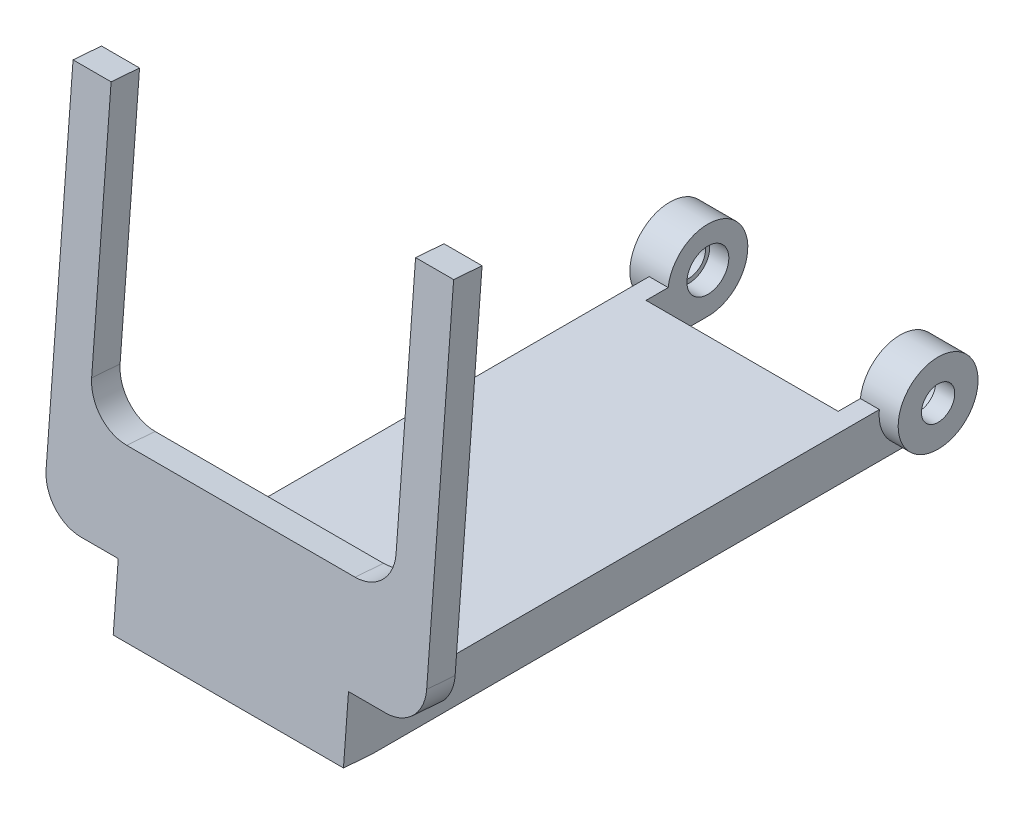
SolidWorks part; units mm, degrees
ref_plane "前视基准面" through (0, 0, 0) normal (0, 0, 1) x (1, 0, 0)
ref_plane "上视基准面" through (0, 0, 0) normal (0, 1, 0) x (1, 0, 0)
ref_plane "右视基准面" through (0, 0, 0) normal (1, 0, 0) x (0, 0, -1)
other "Configuration Table"
sketch "草图1" plane through (0, 0, 0) normal (0, 1, 0) x (1, 0, 0)
  line L1 (0, 0) -> (20.2, 0)
  line L2 (0, 0) -> (0, -30)
  line L3 (0, -30) -> (20.2, -30)
  line L4 (20.2, 0) -> (20.2, -30)
  dimension "D1" = 20.2
  dimension "D2" = 30
extrude "凸台-拉伸1" add sketch "草图1" along normal blind 2
sketch "草图2" plane through (0, 0, 0) normal (-1, 0, 0) x (0, 0, 1)
  line L0 (0, 2) -> (30, 2) construction
  line L1 (0, 2) -> (0, 0) construction
  circle A0 centre (-2.5, 1.5) radius 2.2
  circle A2 centre (-2.5, 1.5) radius 4.2
  dimension "D1" = 4.4
  dimension "D2" = 0.5
  dimension "D3" = 2.5
  dimension "D4" = 2
extrude "凸台-拉伸2" add sketch "草图2" along normal blind 2
ref_plane "基准面1" through (10.1, 0, 0) normal (1, 0, 0) x (0, 0, -1)
sketch "草图3" plane through (0, 0, 0) normal (-1, 0, 0) x (0, 0, 1)
  line L5 (1.423, 0) -> (30, 0)
  line L6 (30, 0) -> (30, 2)
  line L7 (30, 2) -> (1.6701, 2)
  line L9 (1.423, 0) -> (30, 0)
  line L10 (30, 0) -> (30, 2)
  line L11 (30, 2) -> (1.6701, 2)
  arc A1 (1.423, 0) -> (1.6701, 2) centre (-2.5, 1.5) ccw
  arc A2 (1.423, 0) -> (1.6701, 2) centre (-2.5, 1.5) ccw
  dimension "D1" = 0
extrude "凸台-拉伸3" add sketch "草图3" along normal up to surface (2 mm away) up to face at (-2, 1.5, 1.7)
mirror "镜向1" about plane through (10.1, 0, 0) normal (1, 0, 0) of "凸台-拉伸3", "凸台-拉伸2"
sketch "草图4" plane through (0, 2, 0) normal (0, 1, 0) x (1, 0, 0)
  line L0 (20.2, 6.7) -> (20.2, -1.6701) construction
  line L1 (0, 0) -> (20.2, 0)
  line L2 (0, 0) -> (0, -4)
  line L3 (0, -4) -> (20.2, -4)
  line L4 (20.2, 0) -> (20.2, -4)
  dimension "D1" = 4
extrude "切除-拉伸1" cut sketch "草图4" against normal up to next
sketch "草图5" plane through (-2, 0, 0) normal (-1, 0, 0) x (0, 0, 1)
  line L0 (-2.5, 1.5) -> (-5.3682, 2.3794) construction
  line L1 (-5.3682, 2.3794) -> (-0.0916, 19.5887) construction
  line L2 (1.6701, 2) -> (57.2725, 2) construction
  line L3 (-0.0916, 19.5887) -> (57.2725, 2) construction
  dimension "D1" = 3
  dimension "D2" = 18
  dimension "D3" = 60
sketch "草图7" plane through (-2, 0, 0) normal (-1, 0, 0) x (0, 0, 1)
  line L0 (30, 0) -> (56.6593, 0)
  line L1 (56.6593, 0) -> (57.2725, 2)
  line L2 (1.6701, 2) -> (57.2725, 2) construction
  line L3 (57.2725, 2) -> (30, 2)
  line L4 (30, 2) -> (30, 0)
  line L5 (-0.0916, 19.5887) -> (57.2725, 2) construction
extrude "凸台-拉伸4" add sketch "草图7" against normal up to surface (24.2 mm away) up to face at (22.2, 1.5, -0.3)
sketch "草图8" plane through (20.2, 0, 0) normal (-1, 0, 0) x (0, 0, 1)
  line L0 (4, 2) -> (3.3868, 0)
  line L1 (1.423, 0) -> (4, 0) construction
  line L2 (3.3868, 0) -> (4, 0)
  line L3 (4, 0) -> (4, 2)
  line L4 (-5.3682, 2.3794) -> (-0.0916, 19.5887) construction
extrude "凸台-拉伸5" add sketch "草图8" along normal up to surface (20.2 mm away) up to face at (0, 1.2538, 0.7196)
sketch "草图10" plane through (-2, 0, 0) normal (-1, 0, 0) x (0, 0, 1)
  line L0 (56.6593, 0) -> (55.8314, -2.7)
  line L1 (55.8314, -2.7) -> (-2.5, -2.7)
  line L2 (1.423, 0) -> (56.6593, 0)
  line L3 (56.6593, 0) -> (57.2725, 2) construction
  arc A0 (1.6701, 2) -> (1.423, 0) centre (-2.5, 1.5) ccw construction
  arc A1 (-2.5, -2.7) -> (1.423, 0) centre (-2.5, 1.5) ccw
extrude "凸台-拉伸6" add sketch "草图10" against normal up to surface (24.2 mm away) up to face at (22.2, 1.5, -0.3)
sketch "草图11" plane through (20.2, 0, 0) normal (-1, 0, 0) x (0, 0, 1)
  line L0 (3.3868, 0) -> (2.5589, -2.7)
  line L1 (2.5589, -2.7) -> (-2.5, -2.7)
  line L2 (-2.5, -2.7) -> (1.423, 0)
  line L3 (1.423, 0) -> (3.3868, 0)
  line L4 (4, 2) -> (3.3868, 0) construction
extrude "切除-拉伸2" cut sketch "草图11" along normal up to surface (20.2 mm away) up to face at (0, 1.5, -0.3)
sketch "草图12" plane through (0, -15.8797, 51.7903) normal (0, -0.2931, 0.9561) x (1, 0, 0)
  line L0 (10.1, 18.7012) -> (10.1, 38.7012) construction
  line L1 (22.2, 18.7012) -> (-2, 18.7012) construction
  line L2 (10.1, -55) -> (10.1, 55) construction
  line L3 (10.1, 38.7012) -> (-9.9, 38.7012) construction
  line L4 (-9.9, 38.7012) -> (-9.9, -1.2988) construction
  line L5 (-9.9, -1.2988) -> (30.1, -1.2988) construction
  line L6 (30.1, -1.2988) -> (30.1, 38.7012) construction
  line L7 (30.1, 38.7012) -> (10.1, 38.7012) construction
  dimension "D1" = 20
  dimension "D2" = 20
  dimension "D3" = 20
  dimension "D4" = 40
sketch "草图14" plane through (-2, 0, 0) normal (-1, 0, 0) x (0, 0, 1)
  line L3 (-2.5, 1.5) -> (-5.4907, 1.2638) construction
  line L4 (-5.4907, 1.2638) -> (-6.9078, 19.2079) construction
  line L5 (-6.9078, 19.2079) -> (52.9059, 23.9317) construction
  line L6 (-2.5, 1.5) -> (-5.3682, 2.3794) construction
  line L7 (-5.3682, 2.3794) -> (-0.0916, 19.5887) construction
  line L8 (-0.0916, 19.5887) -> (57.2725, 2) construction
  line L9 (1.6701, 2) -> (57.2725, 2) construction
  line L10 (52.9059, 23.9317) -> (54.638, 2) construction
  dimension "D1" = 22
sketch "草图15" plane through (-2, 0, 0) normal (-1, 0, 0) x (0, 0, 1)
  line L0 (51.6286, 2) -> (51.9998, -2.7)
  line L1 (1.6701, 2) -> (57.2725, 2) construction
  line L2 (-2.5, -2.7) -> (55.8314, -2.7) construction
  line L3 (51.9998, -2.7) -> (55.8314, -2.7)
  line L4 (55.8314, -2.7) -> (57.2725, 2)
  line L5 (51.4096, -17.1214) -> (63.1354, 21.1214) construction
  line L6 (57.2725, 2) -> (51.6286, 2)
  line L7 (52.9059, 23.9317) -> (54.638, 2) construction
  dimension "D1" = 3
sketch "草图17" plane through (-2, 0, 0) normal (-1, 0, 0) x (0, 0, 1)
  line L0 (54.638, 2) -> (55.0092, -2.7)
  line L1 (51.9998, -2.7) -> (55.8314, -2.7) construction
  line L2 (55.0092, -2.7) -> (55.8314, -2.7)
  line L3 (55.8314, -2.7) -> (57.2725, 2)
  line L4 (51.4096, -17.1214) -> (63.1354, 21.1214) construction
  line L5 (57.2725, 2) -> (54.638, 2)
  line L6 (52.9059, 23.9317) -> (54.638, 2) construction
extrude "切除-拉伸3" cut sketch "草图17" against normal up to next
sketch "草图18" plane through (0, 4.3007, 54.4563) normal (0, 0.0787, 0.9969) x (1, 0, 0)
  line L0 (-9.9, 39.6922) -> (30.1, -0.3078) construction
  line L1 (-9.9, 39.6922) -> (30.1, 39.6922)
  line L2 (-9.9, 39.6922) -> (-9.9, -0.3078)
  line L3 (-9.9, -0.3078) -> (-2, -0.3078)
  line L4 (30.1, 39.6922) -> (30.1, -0.3078)
  line L5 (-2, 19.6922) -> (10.1, 19.6922) construction
  line L6 (-2, 2.7947) -> (-2, 19.5351) construction
  line L7 (10.1, -2.5152) -> (10.1, 16.0852) construction
  line L8 (-2, -0.3078) -> (-2, -7.0225)
  line L9 (-2, -7.0225) -> (22.2, -7.0225)
  line L10 (22.2, -7.0225) -> (22.2, -0.3078)
  line L11 (22.2, -0.3078) -> (30.1, -0.3078)
  dimension "D1" = 40
extrude "凸台-拉伸7" add sketch "草图18" along normal blind 3
sketch "草图19" plane through (0, 4.5369, 57.447) normal (0, 0.0787, 0.9969) x (1, 0, 0)
  line L0 (30.1, 39.6922) -> (-9.9, 39.6922) construction
  line L1 (-5.9, 39.6922) -> (26.1, 39.6922)
  line L2 (-5.9, 39.6922) -> (-5.9, 9.6922)
  line L3 (-5.9, 9.6922) -> (26.1, 9.6922)
  line L4 (26.1, 39.6922) -> (26.1, 9.6922)
  line L5 (22.2, -0.3078) -> (30.1, -0.3078) construction
  line L6 (-9.9, 39.6922) -> (-9.9, -0.3078) construction
  line L7 (30.1, -0.3078) -> (30.1, 39.6922) construction
  dimension "D1" = 10
  dimension "D2" = 4
  dimension "D3" = 4
extrude "切除-拉伸4" cut sketch "草图19" against normal up to next
fillet "圆角1" radius 4 1 edges at (10.1, 2, 54.638)
fillet "圆角2" radius 4 2 edges at (30.1, 4.0825, 55.6033) (-9.9, 4.0825, 55.6033)
sketch "草图20" plane through (-2, 0, 0) normal (-1, 0, 0) x (0, 0, 1)
  circle A0 centre (-2.5, 1.5) radius 1.75
  circle A1 centre (-2.5, 1.5) radius 4.2
  dimension "D1" = 3.5
extrude "凸台-拉伸8" add sketch "草图20" along normal blind 2
mirror "镜向2" about plane through (10.1, 0, 0) normal (1, 0, 0) of "凸台-拉伸8"
fillet "圆角3" radius 4 2 edges at (26.1, 14.0808, 55.1886) (-5.9, 14.0808, 55.1886)
